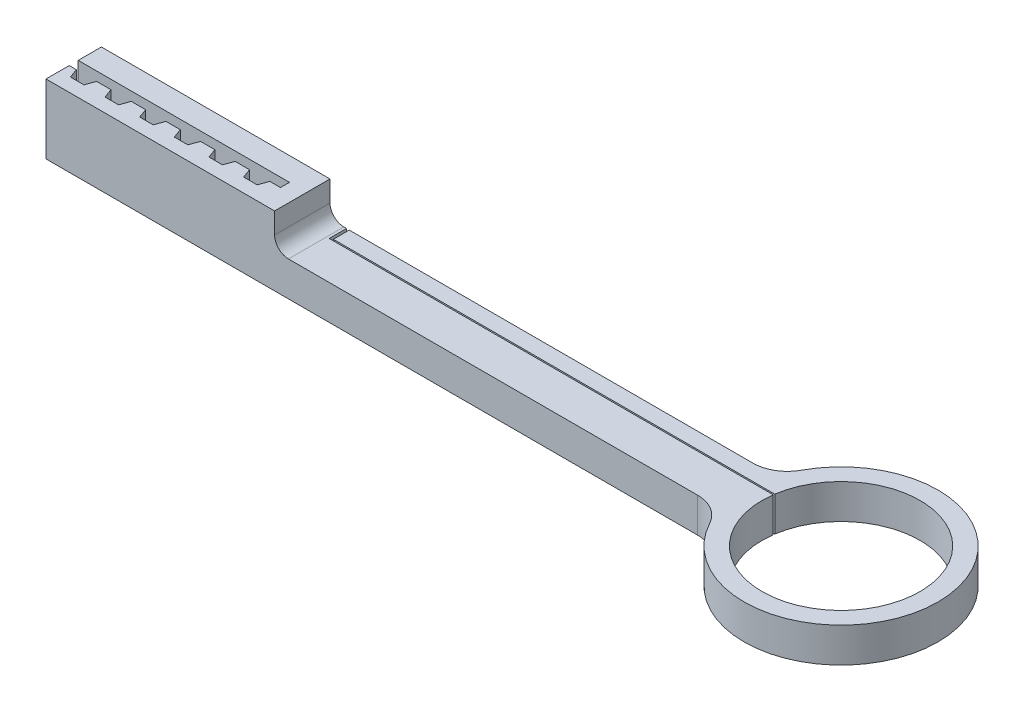
SolidWorks part; units mm, degrees
ref_plane "Спереди" through (0, 0, 0) normal (0, 0, 1) x (1, 0, 0)
ref_plane "Сверху" through (0, 0, 0) normal (0, 1, 0) x (1, 0, 0)
ref_plane "Справа" through (0, 0, 0) normal (1, 0, 0) x (0, 0, -1)
sketch "Эскиз1" plane through (0, 0, 0) normal (0, 1, 0) x (1, 0, 0)
  circle A0 centre (0, 0) radius 11.4
  circle A1 centre (0, 0) radius 14
  dimension "D1" = 22.8
  dimension "D2" = 28
extrude "ring" add sketch "Эскиз1" along normal blind 5
sketch "Эскиз2" plane through (0, 0, 0) normal (0, 1, 0) x (1, 0, 0)
  line L0 (34.0214, 0) -> (-42.1067, 0) construction
  line L1 (-10.7819, 4) -> (-10.7819, -4) construction
  line L2 (-10.7819, 4) -> (-110.7819, 4)
  line L4 (-10.7819, -4) -> (-110.7819, -4)
  line L5 (-110.7819, 4) -> (-110.7819, -4)
  circle A0 centre (0, 0) radius 11.5 construction
  arc A1 (-10.7819, 4) -> (-10.7819, -4) centre (0, 0) ccw
  point P9 (-10.7819, 0)
  dimension "D3" = 23
  dimension "D2" = 8
  dimension "D4" = 100
extrude "stick" add sketch "Эскиз2" along normal blind 5
sketch "Эскиз3" plane through (0, 0, 0) normal (0, 1, 0) x (1, 0, 0)
  line L0 (-110.7819, -4) -> (-13.4164, -4) construction
  line L1 (-110.7819, 4) -> (-77.7819, 4)
  line L2 (-110.7819, 4) -> (-110.7819, -4)
  line L3 (-110.7819, -4) -> (-77.7819, -4)
  line L4 (-77.7819, 4) -> (-77.7819, -4)
  dimension "D1" = 33
extrude "key" add sketch "Эскиз3" along normal blind 10
fillet "Скругление1" radius 5 2 edges at (-13.4164, 2.5, 4) (-13.4164, 2.5, -4)
ref_plane "Плоскость1" through (0, 2.5, 0) normal (0, 1, 0) x (-1, 0, 0)
sketch "Эскиз4" plane through (0, 2.5, 0) normal (0, 1, 0) x (1, 0, 0)
  line L0 (-110.7819, 0) -> (-77.7819, 0) construction
  line L1 (-110.7819, 4) -> (-110.7819, -4) construction
  line L2 (-77.7819, -4) -> (-77.7819, 4) construction
  line L3 (-110.7819, 0.65) -> (-80.2819, 0.65)
  line L4 (-109.2569, -2) -> (-107.3069, -2)
  line L5 (-109.5437, -0.65) -> (-90.7013, -0.65) construction
  line L6 (-109.7483, -0.65) -> (-109.2569, -2) construction
  line L7 (-109.7483, -0.65) -> (-109.2569, -2)
  line L8 (-107.3069, -2) -> (-106.8156, -0.65)
  line L9 (-108.2819, 0.7157) -> (-108.2819, -3.7603) construction
  line L10 (-109.7483, -0.65) -> (-110.7819, -0.65)
  line L11 (-106.8156, -0.65) -> (-105.7819, -0.65)
  line L12 (-110.7819, 0.65) -> (-110.7819, -0.65)
  line L13 (-104.7483, -0.65) -> (-105.7819, -0.65)
  line L14 (-104.2569, -2) -> (-102.3069, -2)
  line L15 (-102.3069, -2) -> (-101.8156, -0.65)
  line L16 (-101.8156, -0.65) -> (-100.7819, -0.65)
  line L17 (-104.7483, -0.65) -> (-104.2569, -2)
  line L18 (-99.7483, -0.65) -> (-100.7819, -0.65)
  line L19 (-99.2569, -2) -> (-97.3069, -2)
  line L20 (-97.3069, -2) -> (-96.8156, -0.65)
  line L21 (-96.8156, -0.65) -> (-95.7819, -0.65)
  line L22 (-99.7483, -0.65) -> (-99.2569, -2)
  line L24 (-94.7483, -0.65) -> (-95.7819, -0.65)
  line L25 (-94.2569, -2) -> (-92.3069, -2)
  line L26 (-92.3069, -2) -> (-91.8156, -0.65)
  line L27 (-91.8156, -0.65) -> (-90.7819, -0.65)
  line L28 (-94.7483, -0.65) -> (-94.2569, -2)
  line L43 (-89.7483, -0.65) -> (-90.7819, -0.65)
  line L44 (-89.2569, -2) -> (-87.3069, -2)
  line L45 (-87.3069, -2) -> (-86.8156, -0.65)
  line L46 (-86.8156, -0.65) -> (-85.7819, -0.65)
  line L47 (-89.7483, -0.65) -> (-89.2569, -2)
  line L48 (-84.7483, -0.65) -> (-85.7819, -0.65)
  line L49 (-84.2569, -2) -> (-82.3069, -2)
  line L50 (-82.3069, -2) -> (-81.8156, -0.65)
  line L51 (-81.8156, -0.65) -> (-80.7819, -0.65)
  line L52 (-84.7483, -0.65) -> (-84.2569, -2)
  line L53 (-80.7819, -0.65) -> (-80.2819, -0.65)
  line L54 (-80.2819, 0.65) -> (-80.2819, -0.65)
  point P12 (-108.2819, -2)
  dimension "D1" = 1.95
  dimension "D2" = 0.65
  dimension "D3" = 0.65
  dimension "D4" = 1.35
  dimension "D5" = 110
  dimension "D6" = 5
  dimension "D7" = 40
  dimension "D8" = 0.5
fillet "Скругление5" radius 2 1 edges at (-77.7819, 5, 0)
extrude "key hole" cut sketch "Эскиз4" against normal through all and the other way through all
sketch "Эскиз5" plane through (0, 0, 0) normal (0, -1, 0) x (1, 0, 0)
  line L0 (0, 0) -> (-70.3859, 0) construction
  line L1 (-75.4, -4) -> (-75.4, -1.5)
  line L3 (-75.4, -1.5) -> (0, -1.5)
  line L4 (0, -1.5) -> (0, -1.7)
  line L5 (0, -1.7) -> (-75, -1.7)
  line L6 (-75, -1.7) -> (-75, -4)
  line L7 (-75, -4) -> (-75.4, -4)
  line L8 (-16.7332, -4) -> (-110.7819, -4) construction
  dimension "D1" = 0.2
  dimension "D2" = 0.4
  dimension "D3" = 75
  dimension "D4" = 1.5
extrude "Вытянуть2" cut sketch "Эскиз5" against normal through all
